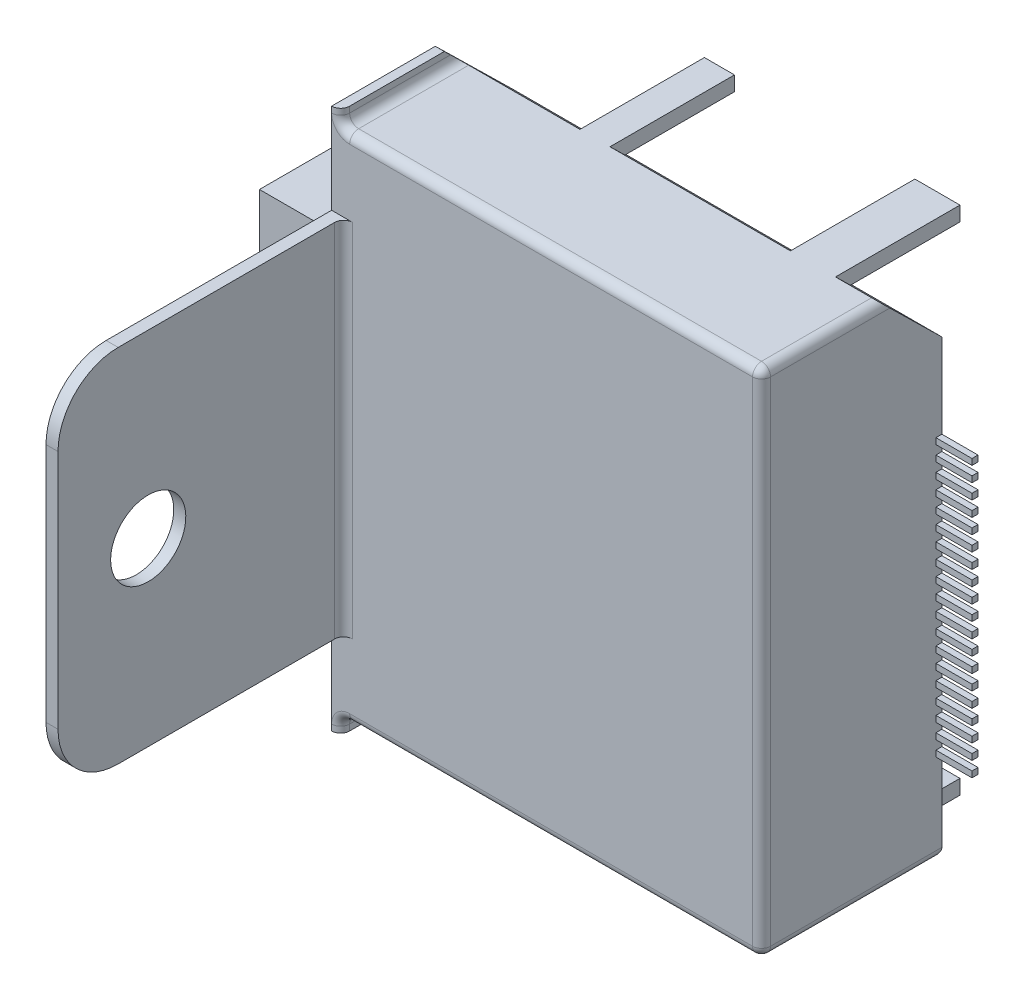
SolidWorks part; units mm, degrees
ref_plane "前视基准面" through (0, 0, 0) normal (0, 0, 1) x (1, 0, 0)
ref_plane "上视基准面" through (0, 0, 0) normal (0, 1, 0) x (1, 0, 0)
ref_plane "右视基准面" through (0, 0, 0) normal (1, 0, 0) x (0, 0, -1)
sketch "草图1" plane through (0, 0, 0) normal (0, 0, 1) x (1, 0, 0)
  line L1 (0, 0) -> (14.3, 0)
  line L2 (0, 0) -> (0, -17)
  line L3 (0, -17) -> (14.3, -17)
  line L4 (14.3, 0) -> (14.3, -17)
  dimension "D1" = 14.3
  dimension "D2" = 17
extrude "凸台-拉伸1" add sketch "草图1" along normal blind 6
sketch "草图3" plane through (14.3, 0, 0) normal (1, 0, 0) x (0, 0, -1)
  line L0 (0, -17) -> (0, 0) construction
  line L1 (0, -14) -> (-0.2, -14)
  line L2 (0, -14) -> (0, -13.8)
  line L3 (0, -13.8) -> (-0.2, -13.8)
  line L4 (-0.2, -14) -> (-0.2, -13.8)
  line L5 (-6, -17) -> (0, -17) construction
  dimension "D1" = 0.2
  dimension "D2" = 0.2
  dimension "D3" = 3
extrude "凸台-拉伸3" add sketch "草图3" along normal blind 1.2
pattern_linear "阵列(线性)1" count 19 spacing 0.5 along (0, 1, 0) of "凸台-拉伸3"
sketch "草图4" plane through (0, 0, 6) normal (0, 0, 1) x (1, 0, 0)
  line L0 (0, -8.5) -> (5.4419, -8.5) construction
  line L1 (0, 0) -> (0.3, 0)
  line L2 (0, 0) -> (0, 0.5)
  line L3 (0, 0.5) -> (0.3, 0.5)
  line L4 (0.3, 0) -> (0.3, 0.5)
  line L5 (0, 0) -> (0, -17) construction
  line L6 (0.3, -17) -> (0.3, -17.5)
  line L7 (0, -17.5) -> (0.3, -17.5)
  line L8 (0, -17) -> (0, -17.5)
  line L9 (0, -17) -> (0.3, -17)
  dimension "D1" = 0.5
  dimension "D2" = 0.3
extrude "凸台-拉伸4" add sketch "草图4" against normal up to surface (6 mm away) up to face at (14.5275, -9.4375, 0)
sketch "草图6" plane through (0, 0, 0) normal (-1, 0, 0) x (0, 0, 1)
  line L0 (0.8143, -1.577) -> (1.8143, -0.577)
  line L1 (1.8143, -0.577) -> (5.0869, -0.577)
  line L2 (0.8143, -1.577) -> (0.8143, -16.5739)
  line L3 (0.8143, -16.5739) -> (5.0869, -16.5739)
  line L4 (5.0869, -0.577) -> (5.0869, -16.5739)
  point P0 (0.8143, -0.577)
  dimension "D3" = 1
extrude "切除-拉伸1" cut sketch "草图6" against normal blind 10
sketch "草图8" plane through (10, 0, 0) normal (-1, 0, 0) x (0, 0, 1)
  line L1 (2.4993, -2.7263) -> (3.3827, -2.7263)
  line L2 (2.4993, -2.7263) -> (2.4993, -14.6574)
  line L3 (2.4993, -14.6574) -> (3.3827, -14.6574)
  line L4 (3.3827, -2.7263) -> (3.3827, -14.6574)
extrude "凸台-拉伸6" add sketch "草图8" along normal blind 5.2
sketch "草图11" plane through (14.3, 0, 0) normal (1, 0, 0) x (0, 0, -1)
  line L0 (-2.745, 0.6907) -> (0.4405, -2.4301)
  line L2 (0.4405, -2.4301) -> (0.4405, 0.6907)
  line L3 (0.4405, 0.6907) -> (-2.745, 0.6907)
extrude "切除-拉伸4" cut sketch "草图11" against normal through all
sketch "草图12" plane through (0, 0, 0) normal (0, 0, -1) x (-1, 0, 0)
  line L0 (-0.3, -17) -> (-14.3, -17) construction
  line L1 (-12.8, -17) -> (-11.3, -17)
  line L2 (-12.8, -17) -> (-12.8, -16.5136)
  line L3 (-12.8, -16.5136) -> (-11.3, -16.5136)
  line L4 (-11.3, -17) -> (-11.3, -16.5136)
  line L5 (-14.3, -17) -> (-14.3, -14) construction
  line L6 (-5.3, -17) -> (-4.3, -17)
  line L7 (-5.3, -17) -> (-5.3, -16.5136)
  line L8 (-5.3, -16.5136) -> (-4.3, -16.5136)
  line L9 (-4.3, -17) -> (-4.3, -16.5136)
  line L10 (-11.6083, -8.5) -> (-1.0437, -8.5) construction
  line L11 (-4.3, 0) -> (-4.3, -0.4864)
  line L12 (-5.3, -0.4864) -> (-4.3, -0.4864)
  line L13 (-5.3, 0) -> (-5.3, -0.4864)
  line L14 (-5.3, 0) -> (-4.3, 0)
  line L15 (-11.3, 0) -> (-11.3, -0.4864)
  line L16 (-12.8, -0.4864) -> (-11.3, -0.4864)
  line L17 (-12.8, 0) -> (-12.8, -0.4864)
  line L18 (-12.8, 0) -> (-11.3, 0)
  dimension "D1" = 10
  dimension "D2" = 1
  dimension "D3" = 1.5
  dimension "D4" = 3
  dimension "D5" = 8.5
extrude "凸台-拉伸7" add sketch "草图12" along normal blind 2.1 and the other way blind 5.2
sketch "草图13" plane through (0, 0, 0) normal (0, 0, -1) x (-1, 0, 0)
  line L0 (-9.3499, -8.7574) -> (-2.5109, -8.7574) construction
  line L1 (0, -1.9985) -> (0, -17.5) construction
  circle A0 centre (-4.5, -8.7574) radius 0.6
  dimension "D1" = 1.2
  dimension "D2" = 4.5
extrude "凸台-拉伸8" add sketch "草图13" along normal blind 2
sketch "草图15" plane through (0, 0, 0) normal (-1, 0, 0) x (0, 0, 1)
  line L1 (6, -8.5) -> (12.7286, -8.5) construction
  line L2 (6, 0.5) -> (6, -17.5) construction
  line L4 (6, -2.5) -> (13.5, -2.5)
  line L5 (6, -2.5) -> (6, -14.5)
  line L6 (6, -14.5) -> (13.5, -14.5)
  line L7 (15.5, -4.5) -> (15.5, -12.5)
  arc A0 (13.5, -14.5) -> (15.5, -12.5) centre (13.5, -12.5) ccw
  arc A1 (15.5, -4.5) -> (13.5, -2.5) centre (13.5, -4.5) ccw
  circle A2 centre (12.5, -8.5) radius 1.25
  dimension "D4" = 2
  dimension "D5" = 2.5
  dimension "D6" = 3
  dimension "D1" = 12
  dimension "D2" = 6
  dimension "D3" = 9.5
extrude "凸台-拉伸9" add sketch "草图15" against normal blind 0.4
sketch "草图16" plane through (0, 0, 0) normal (-1, 0, 0) x (0, 0, 1)
  line L0 (3, -17.5) -> (3, -6.1874) construction
  line L1 (0.9, -4) -> (5.1, -4)
  line L2 (0.9, -4) -> (0.9, -13)
  line L3 (0.9, -13) -> (5.1, -13)
  line L4 (5.1, -4) -> (5.1, -13)
  line L5 (0, -17.5) -> (6, -17.5) construction
  line L6 (15.5, -8.5) -> (-5.1355, -8.5) construction
  line L7 (15.5, -12.5) -> (15.5, -4.5) construction
  dimension "D1" = 4.2
  dimension "D2" = 9
extrude "凸台-拉伸10" add sketch "草图16" along normal blind 3.3
fillet "圆角1" radius 0.3 14 edges at (0.4, -8.5, 6) (14.3, -17, 3) (14.3, 0, 4.02) (14.3, -8.5, 6)
